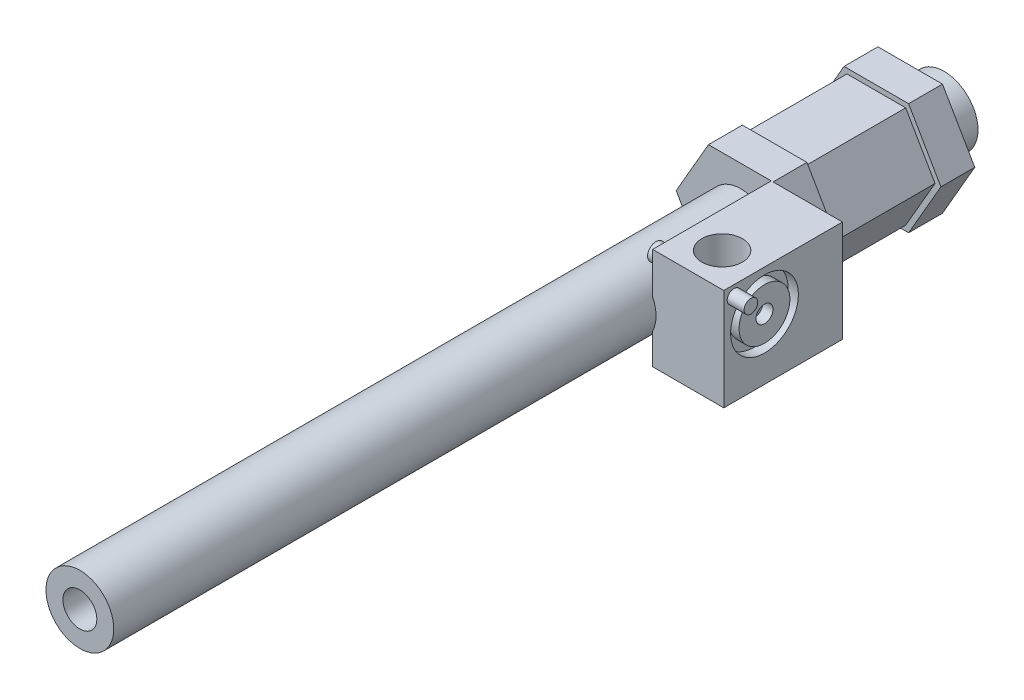
SolidWorks part; units mm, degrees
ref_plane "Front Plane" through (0, 0, 0) normal (0, 0, 1) x (1, 0, 0)
ref_plane "Top Plane" through (0, 0, 0) normal (0, 1, 0) x (1, 0, 0)
ref_plane "Right Plane" through (0, 0, 0) normal (1, 0, 0) x (0, 0, -1)
sketch "Sketch1" plane through (0, 0, 0) normal (0, 0, 1) x (1, 0, 0)
  circle A0 centre (0, 0) radius 10
  dimension "D1" = 20
extrude "Boss-Extrude1" add sketch "Sketch1" along normal blind 255
sketch "Sketch2" plane through (0, 0, 255) normal (0, 0, 1) x (1, 0, 0)
  circle A0 centre (0, 0) radius 5
  dimension "D1" = 10
extrude "Cut-Extrude1" cut sketch "Sketch2" against normal blind 250
sketch "Sketch3" plane through (0, 0, 0) normal (0, 0, -1) x (-1, 0, 0)
  line L1 (17.3205, 0) -> (8.6603, 15)
  line L2 (8.6603, 15) -> (-8.6603, 15)
  line L3 (-8.6603, 15) -> (-17.3205, 0)
  line L4 (-17.3205, 0) -> (-8.6603, -15)
  line L5 (-8.6603, -15) -> (8.6603, -15)
  line L6 (8.6603, -15) -> (17.3205, 0)
  circle A0 centre (0, 0) radius 15 construction
  circle A2 centre (0, 0) radius 10
  circle A3 centre (0, 0) radius 10 construction
  dimension "D1" = 30
extrude "Boss-Extrude2" add sketch "Sketch3" against normal blind 50 from offset 10 offset against normal yes
sketch "Sketch4" plane through (0, 0, 10) normal (0, 0, -1) x (-1, 0, 0)
  line L0 (8.6603, 15) -> (-8.6603, 15) construction
  line L1 (-9.5263, -16.5) -> (9.5263, -16.5)
  line L2 (9.5263, -16.5) -> (19.0526, 0)
  line L3 (19.0526, 0) -> (9.5263, 16.5)
  line L4 (9.5263, 16.5) -> (-9.5263, 16.5)
  line L5 (-9.5263, 16.5) -> (-19.0526, 0)
  line L6 (-19.0526, 0) -> (-9.5263, -16.5)
  line L7 (17.3205, 0) -> (8.6603, 15) construction
  line L8 (8.6603, -15) -> (17.3205, 0) construction
  line L9 (-8.6603, -15) -> (8.6603, -15) construction
  line L10 (-17.3205, 0) -> (-8.6603, -15) construction
  line L11 (-8.6603, 15) -> (-17.3205, 0) construction
  line L12 (8.6603, 15) -> (-8.6603, 15)
  line L13 (17.3205, 0) -> (8.6603, 15)
  line L14 (8.6603, -15) -> (17.3205, 0)
  line L15 (-8.6603, -15) -> (8.6603, -15)
  line L16 (-17.3205, 0) -> (-8.6603, -15)
  line L17 (-8.6603, 15) -> (-17.3205, 0)
  circle A0 centre (0, 0) radius 16.5 construction
  dimension "D1" = 33
extrude "Boss-Extrude3" add sketch "Sketch4" against normal blind 10
extrude "Boss-Extrude4" add sketch "Sketch4<2>" against normal blind 10 from offset 40 offset against normal yes
sketch "Sketch4<2>" plane through (0, 0, 10) normal (0, 0, -1) x (-1, 0, 0) same geometry as "Sketch4"
ref_plane "Plane1" through (10, 0, 0) normal (1, 0, 0) x (0, 0, -1)
sketch "Sketch5" plane through (10, 0, 0) normal (1, 0, 0) x (0, 0, -1)
  line L0 (-60, 16.5) -> (-50, 16.5) construction
  line L1 (-60, 16.5) -> (-95, 16.5)
  line L2 (-60, 16.5) -> (-60, -13.5)
  line L3 (-60, -13.5) -> (-95, -13.5)
  line L4 (-95, 16.5) -> (-95, -13.5)
  line L5 (-60, 10) -> (-60, -10) construction
  dimension "D1" = 35
  dimension "D2" = 30
extrude "Boss-Extrude6" add sketch "Sketch5" along normal blind 10 from offset 10 separate body
sketch "Sketch6" plane through (20, 0, 0) normal (-1, 0, 0) x (0, 0, 1)
  line L4 (60, 16.5) -> (60, -13.5)
  line L5 (60, -13.5) -> (95, -13.5)
  line L6 (95, -13.5) -> (95, 16.5)
  line L7 (95, 16.5) -> (60, 16.5)
  line L8 (60, 16.5) -> (60, -13.5)
  line L9 (60, -13.5) -> (95, -13.5)
  line L10 (95, -13.5) -> (95, 16.5)
  line L11 (95, 16.5) -> (60, 16.5)
  dimension "D1" = 0
extrude "Boss-Extrude8" add sketch "Sketch6" along normal blind 11
sketch "Sketch7" plane through (0, 16.5, 0) normal (0, 1, 0) x (1, 0, 0)
  line L0 (9, -95) -> (30, -95) construction
  circle A0 centre (19.5, -85) radius 6
  point P5 (19.5, -95)
  dimension "D1" = 12
  dimension "D2" = 10
extrude "Cut-Extrude2" cut sketch "Sketch7" against normal blind 21
sketch "Sketch8" plane through (9, 0, 0) normal (-1, 0, 0) x (0, 0, 1)
  line L0 (95, 4.3589) -> (95, 16.5) construction
  line L1 (95, 16.5) -> (60, 16.5) construction
  circle A0 centre (90, 11.5) radius 2.5
  dimension "D1" = 5
  dimension "D2" = 5
  dimension "D3" = 5
extrude "Boss-Extrude9" add sketch "Sketch8" along normal blind 4
sketch "Sketch9" plane through (30, 0, 0) normal (1, 0, 0) x (0, 0, -1)
  line L0 (-60, 16.5) -> (-95, 16.5) construction
  circle A0 centre (-83, 4.5) radius 10
  circle A1 centre (-83, 4.5) radius 7.5
  circle A2 centre (-83, 4.5) radius 2.5
  dimension "D3" = 20
  dimension "D4" = 15
  dimension "D5" = 5
  dimension "D1" = 12
  dimension "D2" = 12
extrude "Cut-Extrude3" cut sketch "Sketch9" against normal blind 3 contours A0 A1 | A2 region at (30, 4.5, 92.7172) region at (30, 4.5, 83)
sketch "Sketch10" plane through (30, 0, 0) normal (1, 0, 0) x (0, 0, -1)
  line L0 (-60, 16.5) -> (-95, 16.5) construction
  line L1 (-95, 16.5) -> (-95, -13.5) construction
  circle A0 centre (-92, 13.5) radius 2
  dimension "D1" = 4
  dimension "D2" = 3
  dimension "D3" = 3
extrude "Boss-Extrude10" add sketch "Sketch10" along normal blind 5
